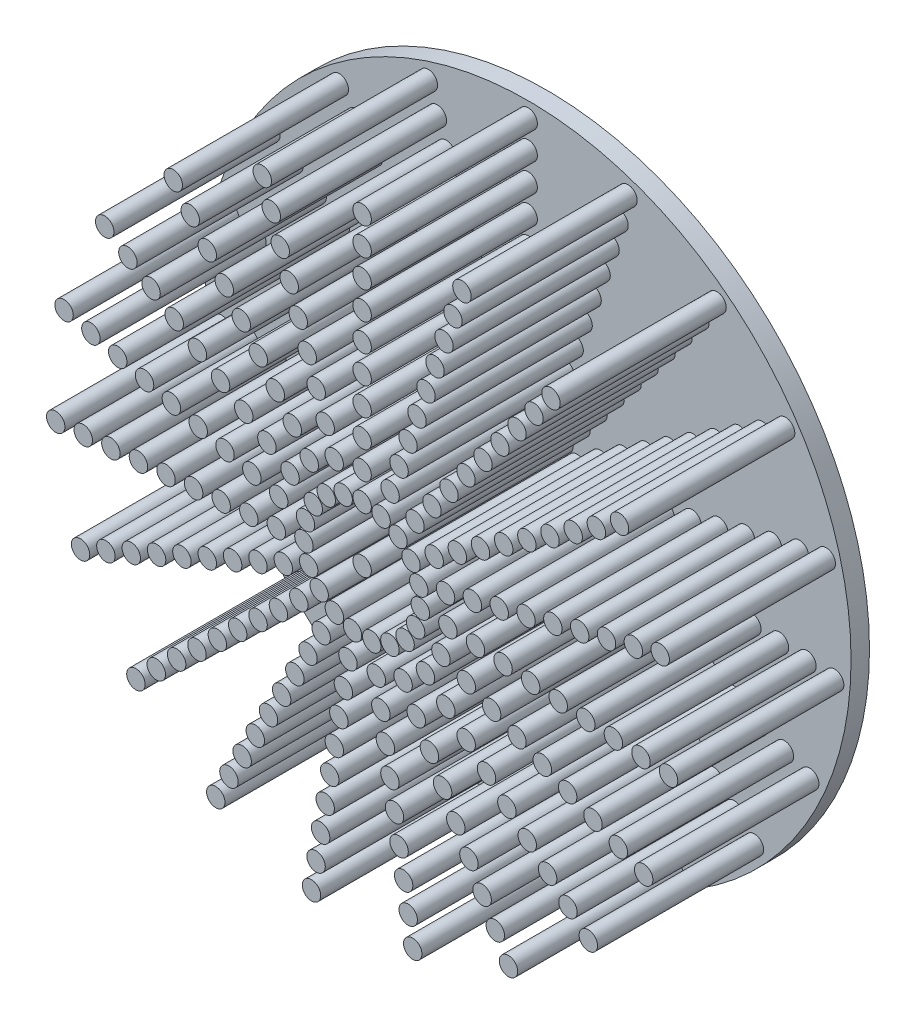
SolidWorks part; units mm, degrees
ref_plane "前视基准面" through (0, 0, 0) normal (0, 0, 1) x (1, 0, 0)
ref_plane "上视基准面" through (0, 0, 0) normal (0, 1, 0) x (1, 0, 0)
ref_plane "右视基准面" through (0, 0, 0) normal (1, 0, 0) x (0, 0, -1)
sketch "草图1" plane through (0, 0, 0) normal (0, 0, 1) x (1, 0, 0)
  circle A0 centre (0, 0) radius 17.5
  dimension "D1" = 35
extrude "凸台-拉伸1" add sketch "草图1" along normal blind 1
sketch "草图2" plane through (0, 0, 1) normal (0, 0, 1) x (1, 0, 0)
  circle A0 centre (0, 16.6648) radius 0.5
  circle A1 centre (0, 15.1648) radius 0.5
  circle A2 centre (0, 13.6648) radius 0.5
  circle A3 centre (0, 12.1648) radius 0.5
  circle A4 centre (0, 10.6648) radius 0.5
  circle A5 centre (0, 9.1648) radius 0.5
  circle A6 centre (0, 7.6648) radius 0.5
  circle A7 centre (0, 6.1648) radius 0.5
  circle A8 centre (0, 4.6648) radius 0.5
  circle A9 centre (0, 3.1648) radius 0.5
  circle A10 centre (0, 1.6648) radius 0.5
  circle A11 centre (0, 0.1648) radius 0.5
  circle A12 centre (5.411, 15.7618) radius 0.5
  circle A13 centre (4.924, 14.3431) radius 0.5
  circle A14 centre (4.4369, 12.9244) radius 0.5
  circle A15 centre (3.9499, 11.5057) radius 0.5
  circle A16 centre (3.4628, 10.0869) radius 0.5
  circle A17 centre (2.9758, 8.6682) radius 0.5
  circle A18 centre (2.4887, 7.2495) radius 0.5
  circle A19 centre (2.0017, 5.8307) radius 0.5
  circle A20 centre (1.5146, 4.412) radius 0.5
  circle A21 centre (1.0276, 2.9933) radius 0.5
  circle A22 centre (10.2357, 13.1508) radius 0.5
  circle A23 centre (9.3144, 11.9671) radius 0.5
  circle A24 centre (8.3931, 10.7834) radius 0.5
  circle A25 centre (7.4718, 9.5997) radius 0.5
  circle A26 centre (6.5504, 8.416) radius 0.5
  circle A27 centre (5.6291, 7.2323) radius 0.5
  circle A28 centre (4.7078, 6.0486) radius 0.5
  circle A29 centre (3.7865, 4.8649) radius 0.5
  circle A30 centre (2.8652, 3.6812) radius 0.5
  circle A31 centre (1.9438, 2.4974) radius 0.5
  circle A32 centre (13.9512, 9.1148) radius 0.5
  circle A33 centre (12.6954, 8.2943) radius 0.5
  circle A34 centre (11.4397, 7.4739) radius 0.5
  circle A35 centre (10.1839, 6.6535) radius 0.5
  circle A36 centre (8.9282, 5.8331) radius 0.5
  circle A37 centre (7.6724, 5.0127) radius 0.5
  circle A38 centre (6.4167, 4.1922) radius 0.5
  circle A39 centre (5.1609, 3.3718) radius 0.5
  circle A40 centre (3.9052, 2.5514) radius 0.5
  circle A41 centre (2.6494, 1.731) radius 0.5
  circle A42 centre (16.1548, 4.091) radius 0.5
  circle A43 centre (14.7007, 3.7227) radius 0.5
  circle A44 centre (13.2466, 3.3545) radius 0.5
  circle A45 centre (11.7925, 2.9863) radius 0.5
  circle A46 centre (10.3384, 2.618) radius 0.5
  circle A47 centre (8.8843, 2.2498) radius 0.5
  circle A48 centre (7.4302, 1.8816) radius 0.5
  circle A49 centre (5.9761, 1.5134) radius 0.5
  circle A50 centre (4.522, 1.1451) radius 0.5
  circle A51 centre (3.0679, 0.7769) radius 0.5
  circle A52 centre (16.6079, -1.3762) radius 0.5
  circle A53 centre (15.113, -1.2523) radius 0.5
  circle A54 centre (13.6181, -1.1284) radius 0.5
  circle A55 centre (12.1232, -1.0046) radius 0.5
  circle A56 centre (10.6283, -0.8807) radius 0.5
  circle A57 centre (9.1335, -0.7568) radius 0.5
  circle A58 centre (7.6386, -0.633) radius 0.5
  circle A59 centre (6.1437, -0.5091) radius 0.5
  circle A60 centre (4.6488, -0.3852) radius 0.5
  circle A61 centre (3.154, -0.2613) radius 0.5
  circle A62 centre (15.2612, -6.6942) radius 0.5
  circle A63 centre (13.8875, -6.0916) radius 0.5
  circle A64 centre (12.5138, -5.4891) radius 0.5
  circle A65 centre (11.1402, -4.8865) radius 0.5
  circle A66 centre (9.7665, -4.284) radius 0.5
  circle A67 centre (8.3929, -3.6814) radius 0.5
  circle A68 centre (7.0192, -3.0789) radius 0.5
  circle A69 centre (5.6455, -2.4764) radius 0.5
  circle A70 centre (4.2719, -1.8738) radius 0.5
  circle A71 centre (2.8982, -1.2713) radius 0.5
  circle A72 centre (12.2607, -11.2867) radius 0.5
  circle A73 centre (11.1571, -10.2708) radius 0.5
  circle A74 centre (10.0535, -9.2549) radius 0.5
  circle A75 centre (8.9499, -8.239) radius 0.5
  circle A76 centre (7.8463, -7.2231) radius 0.5
  circle A77 centre (6.7427, -6.2071) radius 0.5
  circle A78 centre (5.6392, -5.1912) radius 0.5
  circle A79 centre (4.5356, -4.1753) radius 0.5
  circle A80 centre (3.432, -3.1594) radius 0.5
  circle A81 centre (2.3284, -2.1434) radius 0.5
  circle A82 centre (7.9316, -14.6562) radius 0.5
  circle A83 centre (7.2176, -13.337) radius 0.5
  circle A84 centre (6.5037, -12.0178) radius 0.5
  circle A85 centre (5.7898, -10.6986) radius 0.5
  circle A86 centre (5.0759, -9.3794) radius 0.5
  circle A87 centre (4.3619, -8.0602) radius 0.5
  circle A88 centre (3.648, -6.741) radius 0.5
  circle A89 centre (2.9341, -5.4218) radius 0.5
  circle A90 centre (2.2202, -4.1025) radius 0.5
  circle A91 centre (1.5063, -2.7833) radius 0.5
  circle A92 centre (2.7429, -16.4375) radius 0.5
  circle A93 centre (2.496, -14.9579) radius 0.5
  circle A94 centre (2.2491, -13.4784) radius 0.5
  circle A95 centre (2.0023, -11.9989) radius 0.5
  circle A96 centre (1.7554, -10.5193) radius 0.5
  circle A97 centre (1.5085, -9.0398) radius 0.5
  circle A98 centre (1.2616, -7.5602) radius 0.5
  circle A99 centre (1.0147, -6.0807) radius 0.5
  circle A100 centre (0.7678, -4.6012) radius 0.5
  circle A101 centre (0.5209, -3.1216) radius 0.5
  circle A102 centre (-2.7429, -16.4375) radius 0.5
  circle A103 centre (-2.496, -14.9579) radius 0.5
  circle A104 centre (-2.2491, -13.4784) radius 0.5
  circle A105 centre (-2.0023, -11.9989) radius 0.5
  circle A106 centre (-1.7554, -10.5193) radius 0.5
  circle A107 centre (-1.5085, -9.0398) radius 0.5
  circle A108 centre (-1.2616, -7.5602) radius 0.5
  circle A109 centre (-1.0147, -6.0807) radius 0.5
  circle A110 centre (-0.7678, -4.6012) radius 0.5
  circle A111 centre (-0.5209, -3.1216) radius 0.5
  circle A112 centre (-7.9316, -14.6562) radius 0.5
  circle A113 centre (-7.2176, -13.337) radius 0.5
  circle A114 centre (-6.5037, -12.0178) radius 0.5
  circle A115 centre (-5.7898, -10.6986) radius 0.5
  circle A116 centre (-5.0759, -9.3794) radius 0.5
  circle A117 centre (-4.3619, -8.0602) radius 0.5
  circle A118 centre (-3.648, -6.741) radius 0.5
  circle A119 centre (-2.9341, -5.4218) radius 0.5
  circle A120 centre (-2.2202, -4.1025) radius 0.5
  circle A121 centre (-1.5063, -2.7833) radius 0.5
  circle A122 centre (-12.2607, -11.2867) radius 0.5
  circle A123 centre (-11.1571, -10.2708) radius 0.5
  circle A124 centre (-10.0535, -9.2549) radius 0.5
  circle A125 centre (-8.9499, -8.239) radius 0.5
  circle A126 centre (-7.8463, -7.2231) radius 0.5
  circle A127 centre (-6.7427, -6.2071) radius 0.5
  circle A128 centre (-5.6392, -5.1912) radius 0.5
  circle A129 centre (-4.5356, -4.1753) radius 0.5
  circle A130 centre (-3.432, -3.1594) radius 0.5
  circle A131 centre (-2.3284, -2.1434) radius 0.5
  circle A132 centre (-15.2612, -6.6942) radius 0.5
  circle A133 centre (-13.8875, -6.0916) radius 0.5
  circle A134 centre (-12.5138, -5.4891) radius 0.5
  circle A135 centre (-11.1402, -4.8865) radius 0.5
  circle A136 centre (-9.7665, -4.284) radius 0.5
  circle A137 centre (-8.3929, -3.6814) radius 0.5
  circle A138 centre (-7.0192, -3.0789) radius 0.5
  circle A139 centre (-5.6455, -2.4764) radius 0.5
  circle A140 centre (-4.2719, -1.8738) radius 0.5
  circle A141 centre (-2.8982, -1.2713) radius 0.5
  circle A142 centre (-16.6079, -1.3762) radius 0.5
  circle A143 centre (-15.113, -1.2523) radius 0.5
  circle A144 centre (-13.6181, -1.1284) radius 0.5
  circle A145 centre (-12.1232, -1.0046) radius 0.5
  circle A146 centre (-10.6283, -0.8807) radius 0.5
  circle A147 centre (-9.1335, -0.7568) radius 0.5
  circle A148 centre (-7.6386, -0.633) radius 0.5
  circle A149 centre (-6.1437, -0.5091) radius 0.5
  circle A150 centre (-4.6488, -0.3852) radius 0.5
  circle A151 centre (-3.154, -0.2613) radius 0.5
  circle A152 centre (-16.1548, 4.091) radius 0.5
  circle A153 centre (-14.7007, 3.7227) radius 0.5
  circle A154 centre (-13.2466, 3.3545) radius 0.5
  circle A155 centre (-11.7925, 2.9863) radius 0.5
  circle A156 centre (-10.3384, 2.618) radius 0.5
  circle A157 centre (-8.8843, 2.2498) radius 0.5
  circle A158 centre (-7.4302, 1.8816) radius 0.5
  circle A159 centre (-5.9761, 1.5134) radius 0.5
  circle A160 centre (-4.522, 1.1451) radius 0.5
  circle A161 centre (-3.0679, 0.7769) radius 0.5
  circle A162 centre (-13.9512, 9.1148) radius 0.5
  circle A163 centre (-12.6954, 8.2943) radius 0.5
  circle A164 centre (-11.4397, 7.4739) radius 0.5
  circle A165 centre (-10.1839, 6.6535) radius 0.5
  circle A166 centre (-8.9282, 5.8331) radius 0.5
  circle A167 centre (-7.6724, 5.0127) radius 0.5
  circle A168 centre (-6.4167, 4.1922) radius 0.5
  circle A169 centre (-5.1609, 3.3718) radius 0.5
  circle A170 centre (-3.9052, 2.5514) radius 0.5
  circle A171 centre (-2.6494, 1.731) radius 0.5
  circle A172 centre (-10.2357, 13.1508) radius 0.5
  circle A173 centre (-9.3144, 11.9671) radius 0.5
  circle A174 centre (-8.3931, 10.7834) radius 0.5
  circle A175 centre (-7.4718, 9.5997) radius 0.5
  circle A176 centre (-6.5504, 8.416) radius 0.5
  circle A177 centre (-5.6291, 7.2323) radius 0.5
  circle A178 centre (-4.7078, 6.0486) radius 0.5
  circle A179 centre (-3.7865, 4.8649) radius 0.5
  circle A180 centre (-2.8652, 3.6812) radius 0.5
  circle A181 centre (-1.9438, 2.4974) radius 0.5
  circle A182 centre (-5.411, 15.7618) radius 0.5
  circle A183 centre (-4.924, 14.3431) radius 0.5
  circle A184 centre (-4.4369, 12.9244) radius 0.5
  circle A185 centre (-3.9499, 11.5057) radius 0.5
  circle A186 centre (-3.4628, 10.0869) radius 0.5
  circle A187 centre (-2.9758, 8.6682) radius 0.5
  circle A188 centre (-2.4887, 7.2495) radius 0.5
  circle A189 centre (-2.0017, 5.8307) radius 0.5
  circle A190 centre (-1.5146, 4.412) radius 0.5
  circle A191 centre (-1.0276, 2.9933) radius 0.5
  point P387 (0, 0)
  dimension "D1" = 1
  dimension "D2" = 12
  dimension "D3" = 19
extrude "凸台-拉伸2" add sketch "草图2" along normal blind 9
sketch "草图3" plane through (0, 0, 10) normal (0, 0, 1) x (1, 0, 0)
  circle A0 centre (0, 1.6648) radius 0.5
extrude "切除-拉伸1" cut sketch "草图3" against normal up to surface (9 mm away) up to face at (-1.0146, 4.412, 1)
